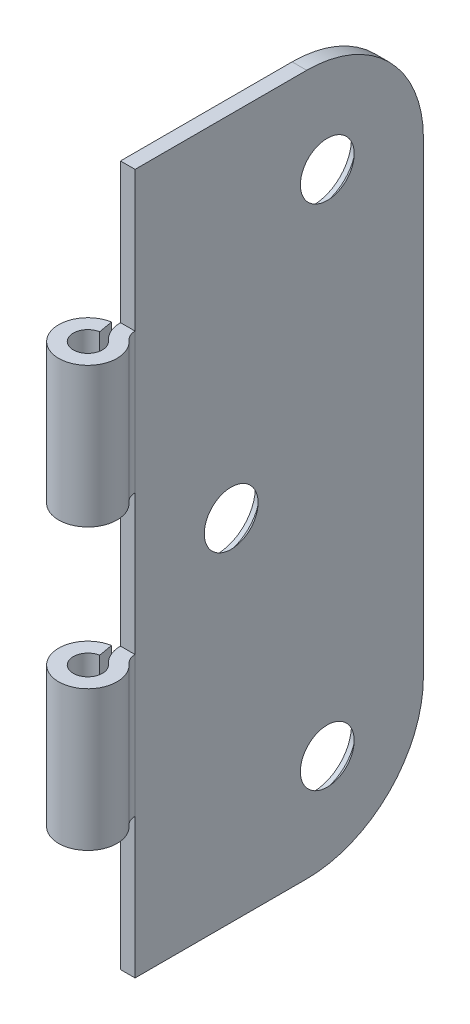
SolidWorks part; units mm, degrees
material "Plain Carbon Steel"
ref_plane "Front Plane" through (0, 0, 0) normal (0, 0, 1) x (1, 0, 0)
ref_plane "Top Plane" through (0, 0, 0) normal (0, 1, 0) x (1, 0, 0)
ref_plane "Right Plane" through (0, 0, 0) normal (1, 0, 0) x (0, 0, -1)
ref_axis "Axis1" through (0, -55, 0) along (0, 1, 0)
sketch "Sketch2" plane through (0, 0, 0) normal (0, 1, 0) x (1, 0, 0)
  line L0 (0, -20.955) -> (0, 20.955) construction
  line L1 (0, 34.925) -> (1.5875, 34.925)
  line L2 (0, 34.925) -> (0, 3.5498)
  line L3 (0, 3.5498) -> (1.5875, 3.5498) construction
  line L4 (1.5875, 34.925) -> (1.5875, 3.5498)
  line L5 (3.175, 0) -> (3.175, 3.5498) construction
  line L6 (-0.5513, 3.1268) -> (0, 0)
  circle A0 centre (0, 0) radius 3.175 construction
  circle A1 centre (0, 0) radius 1.5875 construction
  arc A2 (1.5875, 3.5498) -> (2.1167, 2.3665) centre (3.175, 3.5498) ccw
  arc A3 (0, 3.5498) -> (1.0583, 1.1833) centre (3.175, 3.5498) ccw
  arc A4 (2.1167, 2.3665) -> (-0.5513, 3.1268) centre (0, 0) cw
  circle A5 centre (0, 0) radius 1.5875 construction
  arc A6 (1.0583, 1.1833) -> (-0.2757, 1.5634) centre (0, 0) cw
  point P10 (3.175, 3.5498)
  dimension "D1" = 6.35
  dimension "D2" = 3.175
  dimension "D5" = 31.75
  dimension "D3" = 1.5875
  dimension "D4" = 10
extrude "Boss-Extrude1" add sketch "Sketch2" along normal mid plane 76.2 contours A3 A6 L6 A4 A2 L4 L1 L2 region at (0.5515, 0, -13.0727)
sketch "Sketch3" plane through (0, 0, 0) normal (1, 0, 0) x (0, 0, -1)
  line L0 (3.5498, 38.1) -> (3.5498, -38.1) construction
  line L1 (-3.175, 38.1) -> (-3.175, -38.1) construction
  line L2 (3.5498, 38.1) -> (-3.175, 38.1)
  line L3 (3.5498, 38.1) -> (3.5498, 22.86)
  line L4 (3.5498, 22.86) -> (-3.175, 22.86)
  line L5 (-3.175, 38.1) -> (-3.175, 22.86)
  line L7 (3.5498, 22.86) -> (-3.175, 22.86) construction
  line L8 (3.5498, 22.86) -> (3.5498, 7.62) construction
  line L9 (3.5498, 7.62) -> (-3.175, 7.62) construction
  line L10 (-3.175, 22.86) -> (-3.175, 7.62) construction
  line L11 (3.5498, 7.62) -> (-3.175, 7.62)
  line L12 (3.5498, 7.62) -> (3.5498, -7.62)
  line L13 (3.5498, -7.62) -> (-3.175, -7.62)
  line L14 (-3.175, 7.62) -> (-3.175, -7.62)
  line L15 (3.5498, -7.62) -> (-3.175, -7.62) construction
  line L16 (3.5498, -7.62) -> (3.5498, -22.86) construction
  line L17 (3.5498, -22.86) -> (-3.175, -22.86) construction
  line L18 (-3.175, -7.62) -> (-3.175, -22.86) construction
  line L19 (3.5498, -22.86) -> (-3.175, -22.86)
  line L20 (3.5498, -22.86) -> (3.5498, -38.1)
  line L21 (3.5498, -38.1) -> (-3.175, -38.1)
  line L22 (-3.175, -22.86) -> (-3.175, -38.1)
extrude "Cut-Extrude1" cut sketch "Sketch3" against normal through all and the other way through all
hole_wizard "CSK for #8 Flat Head Machine Screw (100)1" positions "Sketch5" profile "Sketch4" countersink size "#8" standard "ANSI Inch" end condition through all
sketch "Sketch5" plane through (0, 0, 0) normal (-1, 0, 0) x (0, 0, 1)
  line L0 (-34.925, 27.6416) -> (-24.4666, 27.6416) construction
  line L1 (-34.925, 38.1) -> (-34.925, -38.1) construction
  line L2 (-24.4666, 27.6416) -> (-24.4666, 0) construction
  line L3 (-24.4666, 0) -> (-14.0082, 0) construction
  line L4 (-14.0082, 0) -> (-14.0082, 7.62) construction
  line L5 (-14.0082, 7.62) -> (-3.5498, 7.62) construction
  line L9 (-24.4666, 0) -> (-24.4666, -27.6416) construction
  line L11 (-24.4666, 27.6416) -> (-24.4666, 38.1) construction
  line L12 (-34.925, 38.1) -> (-3.5498, 38.1) construction
  point P0 (-24.4666, -27.6416)
  point P2 (-14.0082, 0)
  point P4 (-24.4666, 27.6416)
sketch "Sketch4" plane through (0, -27.6416, -24.4666) normal (0, 1, 0) x (0, 0, 1)
  line L0 (0, 0) -> (0, 3.175)
  line L1 (0, 3.175) -> (2.2479, 3.175)
  line L2 (2.2479, 3.175) -> (2.2479, 2.1598)
  line L3 (2.2479, 2.1598) -> (4.2164, 0.508)
  line L4 (4.2164, 0.508) -> (4.2164, 0)
  line L6 (4.2164, 0) -> (0, 0)
  line L7 (-2.2479, 2.1598) -> (-4.2164, 0.508) construction
  line L11 (0, -6.35) -> (0, 107.95) construction
  dimension "Thru Hole Dia." = 4.4958
  dimension "Thru Hole Depth" = 3.175
  dimension "C'Sink Dia." = 8.4328
  dimension "C'Sink Angle" = 100
  dimension "Head Clearance" = 0.508
fillet "Fillet1" radius 12.7 2 edges at (0.7937, 38.1, -34.925) (0.7937, -38.1, -34.925)
